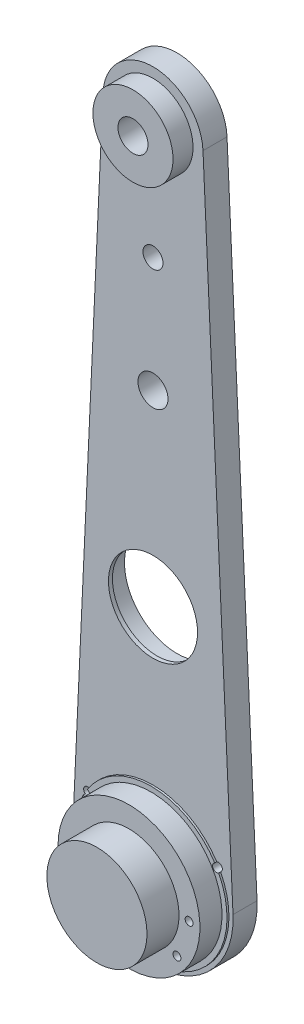
SolidWorks part; units mm, degrees
ref_plane "Front Plane" through (0, 0, 0) normal (0, 0, 1) x (1, 0, 0)
ref_plane "Top Plane" through (0, 0, 0) normal (0, 1, 0) x (1, 0, 0)
ref_plane "Right Plane" through (0, 0, 0) normal (1, 0, 0) x (0, 0, -1)
sketch "Sketch1" plane through (0, 0, 0) normal (0, 0, 1) x (1, 0, 0)
  line L0 (0, 205.4835) -> (0, 0) construction
  line L1 (25.3727, 1.1774) -> (15.8579, 206.2193)
  line L2 (-15.8579, 206.2193) -> (-25.3727, 1.1774)
  circle A1 centre (0, 205.4835) radius 4.7625
  arc A2 (-15.8579, 206.2193) -> (15.8579, 206.2193) centre (0, 205.4835) cw
  arc A3 (-25.3727, 1.1774) -> (25.3727, 1.1774) centre (0, 0) ccw
  dimension "D2" = 15.875
  dimension "D3" = 25.4
  dimension "D4" = 9.525
  dimension "D1" = 205.4835
extrude "Boss-Extrude1" add sketch "Sketch1" along normal mid plane 7.62
sketch "Sketch2" plane through (0, 0, 3.81) normal (0, 0, 1) x (1, 0, 0)
  circle A0 centre (0, 0) radius 22.5
  dimension "D1" = 45
extrude "Boss-Extrude2" add sketch "Sketch2" along normal blind 7.62
sketch "Sketch3" plane through (0, 0, 3.81) normal (0, 0, 1) x (1, 0, 0)
  circle A0 centre (0, 0) radius 24.0899
extrude "Boss-Extrude3" add sketch "Sketch3" along normal offset from surface (0.62 mm away) 7 up to face at (22.5, 0, 11.43)
sketch "Sketch4" plane through (0, 0, 3.81) normal (0, 0, 1) x (1, 0, 0)
  circle A0 centre (0, 73.0199) radius 16.6687
  circle A1 centre (0, 132.4635) radius 4.7625
  circle A2 centre (0, 205.4835) radius 4.7625 construction
  dimension "D2" = 33.3375
  dimension "D3" = 9.525
  dimension "D1" = 73.0199
  dimension "D4" = 73.0199
extrude "Cut-Extrude1" cut sketch "Sketch4" against normal through all both and the other way through all
sketch "Sketch6" plane through (0, 0, 3.81) normal (0, 0, 1) x (1, 0, 0)
  circle A0 centre (0, 73.0199) radius 16.6687
  circle A1 centre (0, 73.0199) radius 14.1287
  circle A2 centre (0, 73.0199) radius 16.6687 construction
  dimension "D1" = 2.54
extrude "Boss-Extrude4" add sketch "Sketch6" against normal offset from surface (1.27 mm away) 6.35 up to face at (16.6687, 73.0199, -3.81)
sketch "Sketch5" plane through (0, 0, 0) normal (0, 0, 1) x (1, 0, 0)
  line L0 (-155.5635, 72.3706) -> (0, 227.9341)
  line L1 (-155.5635, 72.3706) -> (0, -83.1929)
  line L2 (0, 227.9341) -> (155.5635, 72.3706)
  line L3 (0, -83.1929) -> (155.5635, 72.3706)
  line L4 (-155.5635, 72.3706) -> (155.5635, 72.3706) construction
  line L5 (0, 227.9341) -> (0, -83.1929) construction
  arc A1 (15.8579, 206.2193) -> (-15.8579, 206.2193) centre (0, 205.4835) ccw construction
  point P1 (0, 72.3706)
  dimension "D1" = 220
sketch "Sketch7" plane through (0, 0, -3.81) normal (0, 0, -1) x (-1, 0, 0)
  line L1 (-11.7937, -8.3562) -> (-11.7937, 8.3562)
  line L2 (11.7937, -8.3562) -> (11.7937, 8.3562)
  line L3 (-11.7937, 8.3562) -> (11.7937, 8.3562)
  line L4 (-11.7937, -8.3562) -> (11.7937, 8.3562) construction
  line L5 (11.7937, -8.3562) -> (-11.7937, 8.3562) construction
  line L6 (-11, 7.5625) -> (-11.7937, 8.3562) construction
  line L7 (11.7937, 8.3562) -> (11, 7.5625) construction
  line L8 (-11.7937, -8.3562) -> (-11.7937, -22.4959)
  line L10 (11.7937, -22.4959) -> (11.7937, -8.3562)
  line L11 (-11, 7.5625) -> (-11, -20.6542) construction
  arc A0 (-11.7937, -22.4959) -> (11.7937, -22.4959) centre (0, 0) ccw
  arc A1 (-25.3727, 1.1774) -> (25.3727, 1.1774) centre (0, 0) ccw construction
  point P0 (11, 7.5625)
  point P1 (0, 0)
  point P2 (-11, 7.5625)
  point P11 (11, -20.6542)
  dimension "D1" = 0.7937
extrude "Cut-Extrude2" cut sketch "Sketch7" against normal blind 1.5875
sketch "Sketch8" plane through (0, 0, -2.2225) normal (0, 0, -1) x (-1, 0, 0)
  circle A0 centre (9, -5.5625) radius 0.95
  circle A1 centre (-9, -5.5625) radius 0.95
  circle A2 centre (-9, 5.5625) radius 0.95
  circle A3 centre (9, 5.5625) radius 0.95
  dimension "D1" = 1.9
extrude "Cut-Extrude3" cut sketch "Sketch8" against normal through all
sketch "Sketch9" plane through (0, 0, 3.81) normal (0, 0, 1) x (1, 0, 0)
  circle A0 centre (0, 205.4835) radius 12.7
  circle A1 centre (0, 205.4835) radius 4.7625 construction
  circle A2 centre (0, 205.4835) radius 4.7625
  dimension "D1" = 25.4
extrude "Boss-Extrude5" add sketch "Sketch9" along normal blind 6.35
sketch "Sketch10" plane through (0, 0, 11.43) normal (0, 0, 1) x (1, 0, 0)
  circle A0 centre (0, 0) radius 15.875
  dimension "D1" = 31.75
extrude "Boss-Extrude6" add sketch "Sketch10" along normal blind 10.16
sketch "Sketch11" plane through (0, 0, -3.81) normal (0, 0, -1) x (-1, 0, 0)
  circle A0 centre (-20.7431, 11.983) radius 1.25
  circle A1 centre (-19.0618, 0) radius 1.25
  circle A2 centre (-15.2212, -11.4747) radius 1.25
  circle A3 centre (15.2212, -11.4747) radius 1.25
  circle A4 centre (19.0618, 0) radius 1.25
  circle A5 centre (20.7431, 11.983) radius 1.25
  dimension "D1" = 2.5
extrude "Cut-Extrude4" cut sketch "Sketch11" against normal through all both and the other way through all
sketch "Sketch12" plane through (0, 0, 3.81) normal (0, 0, 1) x (1, 0, 0)
  line L0 (0, 205.4835) -> (0, 132.4635) construction
  circle A8 centre (0, 168.9735) radius 3.175
  dimension "D1" = 6.35
extrude "Cut-Extrude5" cut sketch "Sketch12" against normal through all both and the other way through all
equation "\"UpperLinkLength\"= \"LowerFirstStage\" + \"LowerSecondStage\""
equation "\"LowerFirstStage\"= \"60T_20T_171B\""
equation "\"LowerSecondStage\"= \"60T_20T_113B\""
equation "\"D1@Sketch1\"=\"UpperLinkLength\""
equation "\"UpperStage\"= \"60T_20T_113B\""
equation "\"60T_20T_113B\"= 2.8748"
equation "\"60T_20T_171B\"= 5.2151"
equation "\"D1@Sketch4\"=\"UpperStage\""
equation "\"D4@Sketch4\"=\"LowerSecondStage\""
